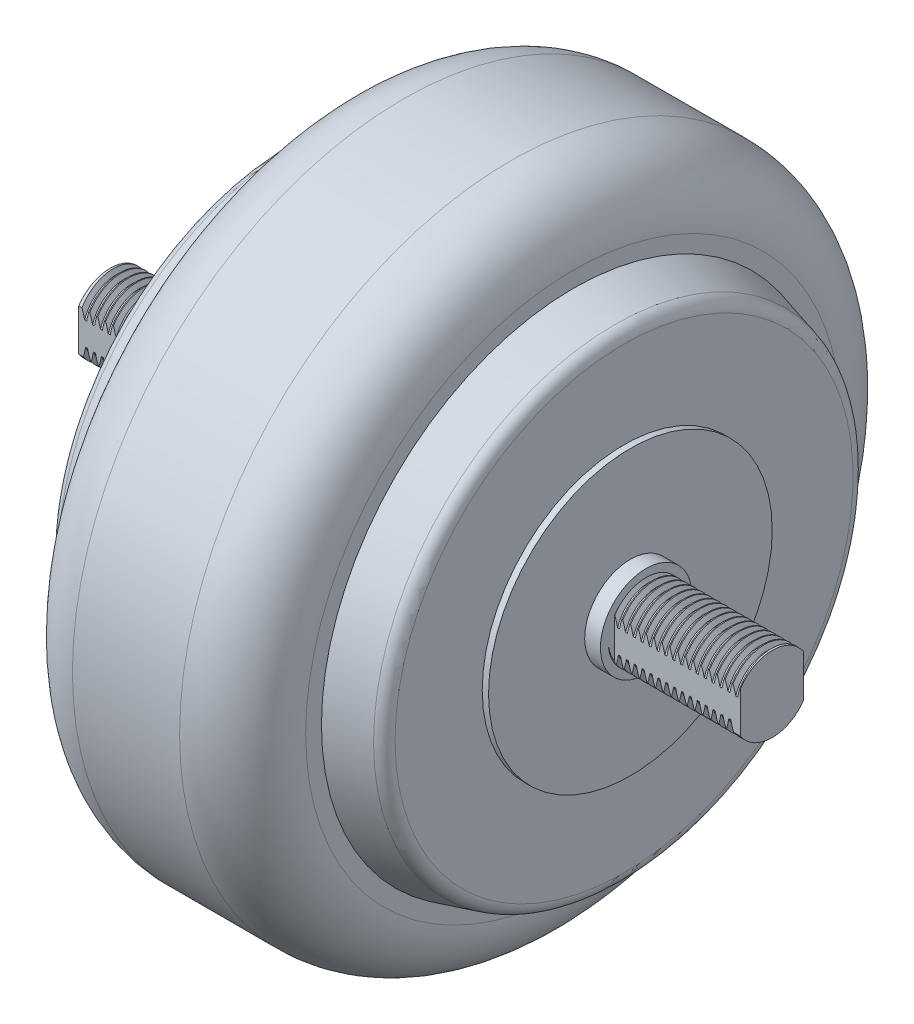
SolidWorks part; units mm, degrees
ref_plane "前视基准面" through (0, 0, 0) normal (0, 0, 1) x (1, 0, 0)
ref_plane "上视基准面" through (0, 0, 0) normal (0, 1, 0) x (1, 0, 0)
ref_plane "右视基准面" through (0, 0, 0) normal (1, 0, 0) x (0, 0, -1)
sketch "草图1" plane through (0, 0, 0) normal (0, 0, 1) x (1, 0, 0)
  line L0 (0, 93.1589) -> (0, -102.4299) construction
  line L1 (-145.9439, 0) -> (135.4766, 0) construction
  line L2 (-18.5, 52.5) -> (18.5, 52.5)
  line L3 (-18.5, 52.5) -> (-18.5, 40)
  line L4 (-18.5, -52.5) -> (18.5, -52.5) construction
  line L5 (18.5, 52.5) -> (18.5, 40)
  line L6 (-18.5, 40) -> (-26.5, 37.8564)
  line L8 (-26.5, 37.8564) -> (-26.5, 22.5)
  line L10 (26.5, 37.8564) -> (26.5, 22.5)
  line L11 (-18.5, -40) -> (-26.5, -37.8564) construction
  line L12 (18.5, -40) -> (26.5, -37.8564) construction
  line L13 (18.5, 40) -> (26.5, 37.8564)
  line L14 (-18.5, -40) -> (-18.5, -52.5) construction
  line L15 (18.5, -40) -> (18.5, -52.5) construction
  line L16 (-28.7704, 40) -> (27.5386, 40) construction
  line L17 (-35.115, -40) -> (32.3474, -40) construction
  line L18 (-26.5, 22.5) -> (-27.5, 22.5)
  line L19 (-27.5, 22.5) -> (-27.5, 7.25)
  line L20 (-27.5, -22.5) -> (-26.5, -22.5) construction
  line L21 (-26.5, -22.5) -> (-26.5, -37.8564) construction
  line L22 (-27.5, 7.25) -> (-30, 7.25)
  line L23 (-30, 7.25) -> (-30, 6)
  line L24 (-30, 6) -> (-55, 6)
  line L25 (-30, -7.25) -> (-30, -6) construction
  line L26 (-27.5, -7.25) -> (-30, -7.25) construction
  line L27 (-30, -6) -> (-55, -6) construction
  line L28 (-55, 6) -> (-55, 0)
  line L29 (-27.5, -7.25) -> (-27.5, -22.5) construction
  line L30 (27.5, -22.5) -> (26.5, -22.5) construction
  line L31 (27.5, -7.25) -> (27.5, -22.5) construction
  line L32 (27.5, -7.25) -> (30, -7.25) construction
  line L33 (30, -7.25) -> (30, -6) construction
  line L34 (30, 7.25) -> (30, 6)
  line L35 (27.5, 7.25) -> (30, 7.25)
  line L36 (27.5, 22.5) -> (27.5, 7.25)
  line L37 (27.5, 22.5) -> (26.5, 22.5)
  line L38 (26.5, -22.5) -> (26.5, -37.8564) construction
  line L39 (30, 6) -> (50, 6)
  line L40 (50, 6) -> (50, 0)
  line L41 (54, -6) -> (30, -6) construction
  line L42 (-55, 0) -> (50, 0)
  dimension "D1" = 105
  dimension "D2" = 37
  dimension "D3" = 53
  dimension "D4" = 80
  dimension "D5" = 75
  dimension "D6" = 1
  dimension "D7" = 45
  dimension "D8" = 12
  dimension "D9" = 14.5
  dimension "D10" = 2.5
  dimension "D11" = 20
  dimension "D12" = 105
revolve "旋转2" add sketch "草图1" angle 360 about L1
fillet "圆角1" radius 10 2 edges at (-18.5, 0, 52.5) (18.5, 0, 52.5)
fillet "圆角2" radius 2 2 edges at (-26.5, 0, 37.8564) (26.5, 0, 37.8564)
thread "螺纹线1" pitch 1.25 start angle 0, offset 0, length 15, pitch 1.25, diameter 12
ref_plane "基准面1" through (-55, 0, -6) normal (0, -1, 0) x (0, 0, -1)
sketch "螺纹线轮廓1" plane through (-55, 0, -6) normal (0, -1, 0) x (0, 0, -1)
  line L0 (0, 0) -> (0, 1.25) construction
  line L11 (0, 0) -> (0, 1.0937)
  line L12 (0, 1.0937) -> (-0.6766, 0.7031)
  line L13 (-0.6766, 0.7031) -> (-0.6766, 0.3906)
  line L15 (-0.6766, 0.3906) -> (0, 0)
  line L17 (-0.6766, 0.5469) -> (0, 0.5469) construction
  point P2 (0, 0)
  dimension "Pitch" = 1.25
  dimension "Profile_Angle" = 60
  dimension "Profile_Land" = 0.3125
  dimension "Profile_Height" = 0.6766
thread "螺纹线2" pitch 1.25 profile "螺纹线轮廓2" start angle 0, offset 0, length 20, pitch 1.25, diameter 12
ref_plane "基准面2" through (50, 0, 6) normal (0, -1, 0) x (0, 0, 1)
sketch "螺纹线轮廓2" plane through (50, 0, 6) normal (0, -1, 0) x (0, 0, 1)
  line L0 (0, 0) -> (0, 1.25) construction
  line L11 (0, 0) -> (0, 1.0937)
  line L12 (0, 1.0937) -> (-0.6766, 0.7031)
  line L13 (-0.6766, 0.7031) -> (-0.6766, 0.3906)
  line L15 (-0.6766, 0.3906) -> (0, 0)
  line L17 (-0.6766, 0.5469) -> (0, 0.5469) construction
  point P2 (0, 0)
  dimension "Pitch" = 1.25
  dimension "Profile_Angle" = 60
  dimension "Profile_Land" = 0.3125
  dimension "Profile_Height" = 0.6766
sketch "草图9" plane through (-55, 0, 0) normal (-1, 0, 0) x (0, 0, 1)
  line L0 (0, 11.1834) -> (0, -10.9047) construction
  line L1 (-5, 3.3166) -> (-5, -3.3166)
  line L2 (5, 3.3166) -> (5, -3.3166)
  arc A0 (-5, 3.3166) -> (-5, -3.3166) centre (0, 0) ccw
  arc A1 (5, -3.3166) -> (5, 3.3166) centre (0, 0) ccw
  dimension "D2" = 6
  dimension "D1" = 10
extrude "切除-拉伸1" cut sketch "草图9" against normal up to surface (25 mm away) up to face at (-30, 0, 6)
sketch "草图10" plane through (50, 0, -54) normal (-1, 0, 0) x (0, 0, 1)
  line L0 (54, 11.1834) -> (54, -10.9047) construction
  line L1 (49, 3.3166) -> (49, -3.3166)
  line L2 (59, 3.3166) -> (59, -3.3166)
  arc A0 (49, 3.3166) -> (49, -3.3166) centre (54, 0) ccw
  arc A1 (59, -3.3166) -> (59, 3.3166) centre (54, 0) ccw
  dimension "D2" = 6
  dimension "D1" = 10
extrude "切除-拉伸2" cut sketch "草图10" along normal blind 20
